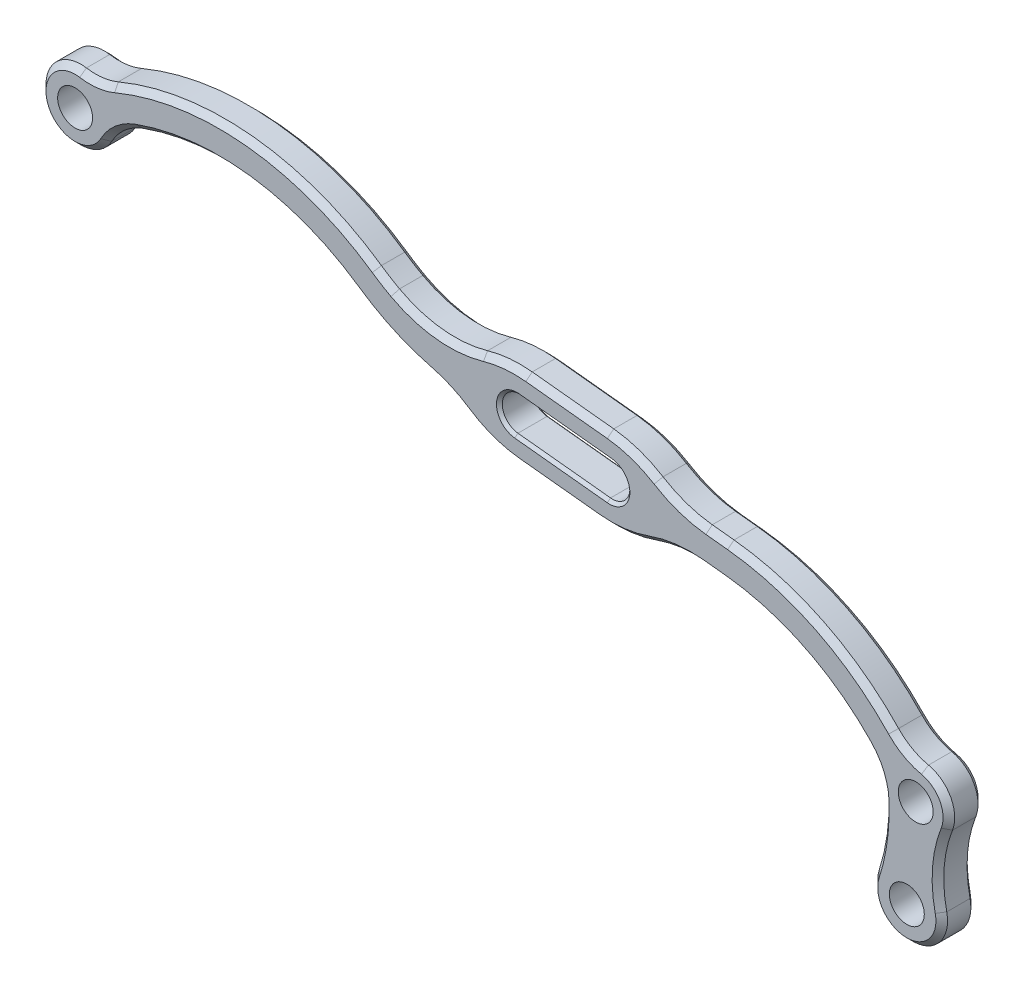
SolidWorks part; units mm, degrees
ref_plane "Спереди" through (0, 0, 0) normal (0, 0, 1) x (1, 0, 0)
ref_plane "Сверху" through (0, 0, 0) normal (0, 1, 0) x (1, 0, 0)
ref_plane "Справа" through (0, 0, 0) normal (1, 0, 0) x (0, 0, -1)
other "Configuration Table"
sketch "Sketch1" plane through (0, 0, 5) normal (0, 0, 1) x (1, 0, 0)
  line L0 (72.4787, 6.0336) -> (94.9418, 3.6726)
  line L1 (80.4883, 8.2083) -> (89.9363, 7.2152) construction
  line L2 (36.385, 6.5) -> (39, 6.5)
  line L3 (35.2523, 11.1565) -> (36.385, 6.5)
  line L4 (80.4883, 8.2083) -> (89.9363, 7.2152) construction
  arc A0 (40.881, 10.4938) -> (63.9587, 9.1988) centre (51.3653, -8.9473) cw
  circle A1 centre (111.1997, -6.0169) radius 2.85
  arc A2 (39, 6.5) -> (37.6854, 12.1966) centre (39, 9.5) ccw
  arc A3 (35.2523, 11.1565) -> (37.6854, 12.1966) centre (26, 36.1667) ccw
  arc A4 (39, 6.5) -> (37.6854, 12.1966) centre (39, 9.5) ccw construction
  circle A6 centre (111.1997, -6.0169) radius 2.85
  circle A7 centre (110.4359, -14.0152) radius 1.5 construction
  circle A8 centre (110.4359, -14.0152) radius 3
  circle A9 centre (110.4359, -14.0152) radius 1.5
  circle A10 centre (111.1997, -6.0169) radius 1.5
  arc A11 (108.36, -6.2592) -> (107.5809, -13.0939) centre (90.9923, -7.7411) cw
  arc A12 (113.8545, -7.0535) -> (113.3652, -13.3677) centre (124.0032, -11.016) ccw
  circle A13 centre (39, 9.5) radius 3
  circle A14 centre (39, 9.5) radius 1.5
  arc A15 (63.9587, 9.1988) -> (72.4787, 6.0336) centre (74.3914, 24.2316) ccw
  arc A17 (94.9418, 3.6726) -> (109.7835, -4.7641) centre (92.7146, -17.5185) cw
  circle A18 centre (84.8987, 4.7282) radius 1.5 construction
  circle A19 centre (84.8987, 4.7282) radius 1.5
  arc A22 (64.2892, 10.447) -> (76.3424, 5.2756) centre (78.6577, 27.304) ccw construction
  point P21 (0, 0)
  point P23 (40.8465, 10.4974)
  point P26 (109.7835, -4.7641)
  point P33 (0, 0)
  point P34 (73.4577, 5.9307)
  point P35 (63.4843, 9.5)
  point P39 (72.446, 6.0431)
  circle M8 centre (39, 9.5) radius 1.5
  arc M10 (39, 6.5) -> (37.6854, 12.1966) centre (39, 9.5) ccw
  dimension "D3" = 6
  dimension "D4" = 3
  dimension "D5" = 6
  dimension "D6" = 3
  dimension "D1" = 0
  dimension "D2" = 0
extrude "Boss-Extrude1" add sketch "Sketch1" along normal blind 3 contours A13 M10 M8 | A6 A10 | A12 A6 A11 A8 | A8 A9 region at (112.2601, -3.4586, 5) region at (41.8306, 10.1969, 5) region at (110.6816, -9.9328, 5) region at (110.5737, -11.1033, 5)
sketch "Sketch3" plane through (0, 0, 5) normal (0, 0, 1) x (1, 0, 0)
  line L0 (72.4787, 6.0336) -> (94.9418, 3.6726) construction
  line L1 (72.4787, 6.0336) -> (94.9418, 3.6726)
  arc A0 (109.7835, -4.7641) -> (94.9418, 3.6726) centre (92.7146, -17.5185) ccw construction
  arc A1 (63.9587, 9.1988) -> (72.4787, 6.0336) centre (74.3914, 24.2316) ccw construction
  arc A2 (63.9587, 9.1988) -> (40.881, 10.4938) centre (51.3653, -8.9473) ccw construction
  arc A3 (109.7835, -4.7641) -> (94.9418, 3.6726) centre (92.7146, -17.5185) ccw
  arc A4 (63.9587, 9.1988) -> (72.4787, 6.0336) centre (74.3914, 24.2316) ccw
  arc A5 (63.9587, 9.1988) -> (40.881, 10.4938) centre (51.3653, -8.9473) ccw
extrude "Extrude-Thin1" add sketch "Sketch3" along normal blind 3 thin thin type mid plane wall 3
sketch "Sketch4" plane through (0, 0, 8) normal (0, 0, 1) x (1, 0, 0)
  line L0 (71.8385, 9.6201) -> (90.7344, 7.6341)
  line L1 (71.8385, 9.6201) -> (71.1068, 2.6585)
  line L2 (90.7344, 7.6341) -> (90.0027, 0.6724)
  line L3 (71.1068, 2.6585) -> (90.0027, 0.6724)
  line L4 (95.0986, 5.1644) -> (72.6355, 7.5254) construction
  line L5 (95.0986, 5.1644) -> (72.6355, 7.5254) construction
  line L7 (94.785, 2.1808) -> (72.3219, 4.5418) construction
  line L8 (76.9425, 5.5644) -> (84.8987, 4.7282) construction
  line L9 (77.0993, 7.0562) -> (85.0555, 6.22)
  line L10 (76.7857, 4.0726) -> (84.7419, 3.2364)
  circle A36 centre (84.8987, 4.7282) radius 1.5
  circle A37 centre (84.8987, 4.7282) radius 1.5 construction
  arc A38 (77.0993, 7.0562) -> (76.7857, 4.0726) centre (76.9425, 5.5644) ccw
  arc A39 (84.7419, 3.2364) -> (85.0555, 6.22) centre (84.8987, 4.7282) ccw
  point P5 (80.9206, 5.1463)
  point P17 (78.5119, 5.3996)
  dimension "D1" = 2
  dimension "D4" = 1.5
  dimension "D7" = 4
  dimension "D2" = 2
  dimension "D5" = 8
  dimension "D6" = 4
  dimension "D3" = 0
extrude "Boss-Extrude2" add sketch "Sketch4" against normal up to surface (3 mm away) up to face at (86.0676, 0.9668, 5)
fillet "Fillet1" radius 10 4 edges at (90.0027, 0.6724, 6.5) (90.7344, 7.6341, 6.5) (71.1068, 2.6585, 6.5) (71.8385, 9.6201, 6.5)
fillet "Fillet2" radius 10 4 edges at (90.2118, 2.6615, 6.5) (71.3186, 4.6732, 6.5) (71.6326, 7.6614, 6.5) (90.5254, 5.6451, 6.5)
fillet "Fillet3" radius 5 4 edges at (108.4097, -5.435, 6.5) (110.5094, -3.2518, 6.5) (41.9978, 9.3861, 6.5) (40.5973, 12.0394, 6.5)
extrude "Cut-Extrude2" cut sketch "Sketch4<2>" against normal blind 3 contours A38 L10 A39 L9
sketch "Sketch4<2>" plane through (0, 0, 8) normal (0, 0, 1) x (1, 0, 0) same geometry as "Sketch4"
chamfer "Chamfer1" distance 0.25 angle 45 8 edges at (86.3905, 4.5714, 5) (81.0774, 6.6381, 5) (80.7638, 3.6545, 5) (75.4508, 5.7212, 5) (86.3905, 4.5714, 8) (81.0774, 6.6381, 8) (80.7638, 3.6545, 8) (75.4508, 5.7212, 8)
fillet "Fillet4" radius 0.5 54 edges at (75.8318, 9.0125, 5) (81.2661, 8.6293, 5) (86.9646, 7.7757, 5) (91.0309, 5.8465, 5) (94.1635, 5.2627, 5) (102.7851, 2.9457, 5) (110.4079, -2.7042, 5) (113.7101, -4.6677, 5) (113.1409, -10.1742, 5) (110.2941, -17.0118, 5) (108.2583, -10.1322, 5) (108.0198, -5.3349, 5) (101.4396, 0.2642, 5) (93.8499, 2.2791, 5) (90.6644, 2.3593, 5) (86.2859, 1.3177, 5) (80.5718, 1.6637, 5) (74.7466, 2.5711, 5) (66.1672, 6.2223, 5) (54.0154, 11.4693, 5) (42.7734, 9.4873, 5) (36.3099, 8.172, 5) (40.8653, 12.4347, 5) (53.8144, 14.5131, 5) (65.5775, 9.9313, 8) (75.8318, 9.0125, 8) (81.2661, 8.6293, 8) (86.9646, 7.7757, 8) (91.0309, 5.8465, 8) (94.1635, 5.2627, 8) (102.7851, 2.9457, 8) (110.4079, -2.7042, 8) (113.7101, -4.6677, 8) (113.1409, -10.1742, 8) (110.2941, -17.0118, 8) (108.2583, -10.1322, 8) (108.0198, -5.3349, 8) (101.4396, 0.2642, 8) (93.8499, 2.2791, 8) (90.6644, 2.3593, 8) (86.2859, 1.3177, 8) (80.5718, 1.6637, 8) (74.7466, 2.5711, 8) (66.1672, 6.2223, 8) (54.0154, 11.4693, 8) (42.7734, 9.4873, 8) (36.3099, 8.172, 8) (40.8653, 12.4347, 8) (65.5775, 9.9313, 5) (53.8144, 14.5131, 8) (70.0687, 8.3171, 5) (71.0975, 4.4899, 5) (70.0687, 8.3171, 8) (71.0975, 4.4899, 8) profile chamfer
